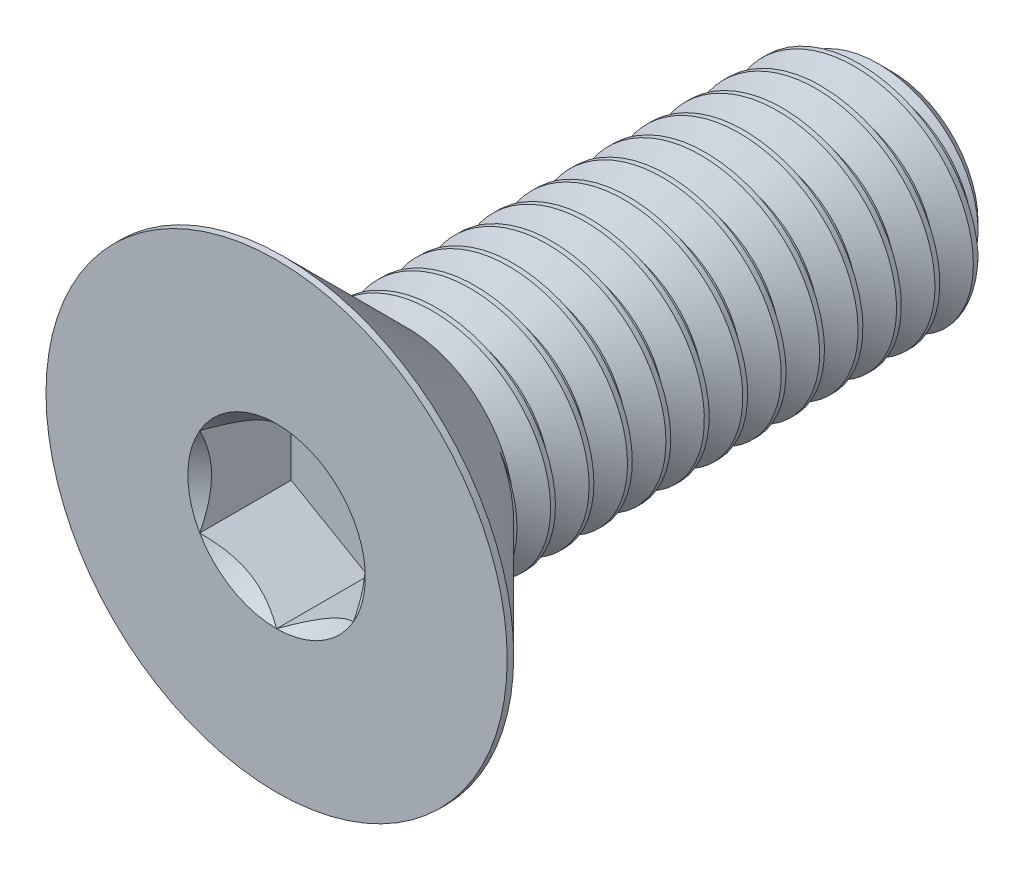
SolidWorks part; units mm, degrees
ref_plane "Front" through (0, 0, 0) normal (0, 0, 1) x (1, 0, 0)
ref_plane "Top" through (0, 0, 0) normal (0, 1, 0) x (1, 0, 0)
ref_plane "Right" through (0, 0, 0) normal (1, 0, 0) x (0, 0, -1)
sketch "Sketch11" plane through (0, 0, 0) normal (1, 0, 0) x (0, 0, -1)
  line L0 (-4, 3) -> (4, 3) construction
  line L5 (-4, 3) -> (-4, -3) construction
  line L6 (4, 1.5) -> (4, -1.5) construction
  line L7 (-3.99, 1) -> (-3.99, -1) construction
  line L8 (3.9687, 1.5541) -> (4.4687, 1.5541) construction
  line L9 (4.4687, 1.5541) -> (4.2187, 1.1211) construction
  line L10 (4.2187, 1.1211) -> (3.9687, 1.5541) construction
  line L11 (4.1875, 1.1752) -> (4.25, 1.1752) construction
  line L12 (4.2187, 1.1752) -> (4.2187, 1.1211) construction
  line L13 (3.9844, 1.5271) -> (4.4531, 1.5271) construction
  line L14 (4.2187, 1.5541) -> (4.2187, 1.5) construction
  line L15 (4, 1.5) -> (4.4375, 1.5) construction
  line L17 (-3.915, 3) -> (-0.915, 0) construction
  line L18 (-0.915, 0) -> (-3.915, -3) construction
  point P3 (-2.3, 3)
  point P8 (0, 3)
  point P21 (4.2187, 1.5271)
  point P26 (-4, 0)
  point P28 (-3.99, 0)
  point P29 (4, 0)
  dimension "Length" = 8
  dimension "Head Diameter" = 6
  dimension "Thread Major Diameter" = 3
  dimension "Head Height" = 1.7
  dimension "Drive Size" = 2
  dimension "Thread Pitch" = 0.5
  dimension "D1" = 0.0625
  dimension "D2" = 0.01
  dimension "D3" = 0.085
  dimension "Countersink Angle" = 90
sketch "Sketch1" plane through (0, 0, 0) normal (1, 0, 0) x (0, 0, -1)
  line L2 (-2.3, 1.5) -> (4, 1.5)
  line L3 (4, 1.5) -> (4, 0)
  line L4 (-2.81, 1.5) -> (-2.81, 0)
  line L5 (-2.3, 1.5) -> (-2.81, 1.5)
  line L6 (-4, 3) -> (-4, -3) construction
  line L7 (4, 1.5) -> (4, -1.5) construction
  line L8 (-2.81, 0) -> (4, 0)
  dimension "D1" = 1.19
revolve "Revolve1" add sketch "Sketch1" angle 360 mid plane about L8
chamfer "Chamfer1" distance 0.375 angle 45 1 edges at (1.5, 0, -4)
sketch "Sketch7" plane through (0, 0, 0) normal (1, 0, 0) x (0, 0, -1)
  line L2 (-4, 3) -> (-3.915, 3)
  line L5 (-2.3, 1.385) -> (-2.3, 0)
  line L6 (-4, 3) -> (-4, 0)
  line L8 (-4, 3) -> (-4, -3) construction
  line L9 (-4, 0) -> (-2.3, 0)
  line L12 (-3.915, 3) -> (-2.3, 1.385)
  line L13 (-3.915, 3) -> (-0.915, 0) construction
revolve "Revolve2" add sketch "Sketch7" angle 360 mid plane about L9 region at (0, 1.1696, 3.2571)
ref_plane "Plane1" through (0, 0, 2.3) normal (0, 0, 1) x (1, 0, 0)
sketch "Sketch5" plane through (0, 0, 4) normal (0, 0, 1) x (1, 0, 0)
  line L1 (1, -0.5774) -> (1, 0.5774)
  line L2 (1, 0.5774) -> (0, 1.1547)
  line L3 (0, 1.1547) -> (-1, 0.5774)
  line L4 (-1, 0.5774) -> (-1, -0.5774)
  line L5 (-1, -0.5774) -> (0, -1.1547)
  line L6 (0, -1.1547) -> (1, -0.5774)
  circle A0 centre (0, 0) radius 1 construction
extrude "Cut-Extrude2" cut sketch "Sketch5" against normal blind 1.19
sketch "Sketch6" plane through (0, 0, 4) normal (0, 0, -1) x (-1, 0, 0)
  circle A0 centre (0, 0) radius 1.1547
extrude "Cut-Extrude3" cut sketch "Sketch6" along normal blind 1.19 draft 45
sketch "Sketch12" plane through (0, 0, -4) normal (0, 0, -1) x (-1, 0, 0)
  circle A0 centre (0, 0) radius 1.5 construction
  circle A1 centre (0, 0) radius 1.5
curve "Helix/Spiral1" pitch 0.5 height 8 radius 1.5 centre (0, 0, -4) axis (0, 0, 1) start towards (0, 1, 0)
sketch "Sketch13" plane through (0, 0, 0) normal (1, 0, 0) x (0, 0, -1)
  line L0 (3.9844, 1.5271) -> (4.4531, 1.5271)
  line L1 (4.4531, 1.5271) -> (4.25, 1.1752)
  line L2 (4.25, 1.1752) -> (4.1875, 1.1752)
  line L3 (4.1875, 1.1752) -> (3.9844, 1.5271)
sweep "Cut-Sweep1" cut profiles "Sketch13" path "Helix/Spiral1" align with end faces yes
combine bodies "Combine1" operation type add bodies to combine 113 127
equation "\"D1@Chamfer1\"=\"Thread Pitch@Sketch11\" * .75"
equation "\"D1@Cut-Extrude2\"= \"Head Height@Sketch11\" * .7"
equation "\"D1@Cut-Extrude3\" = \"D1@Cut-Extrude2\""
equation "\"D1@Sketch11\"=\"Thread Pitch@Sketch11\"/8"
equation "\"D3@Sketch11\"=\"Head Height@Sketch11\"*.05"
equation "\"D4@Helix/Spiral1\"=\"Thread Pitch@Sketch11\""
equation "\"D1@Sketch1\"=\"Head Height@Sketch11\"*.7"
equation "\"D3@Helix/Spiral1\"=\"Length@Sketch11\""
